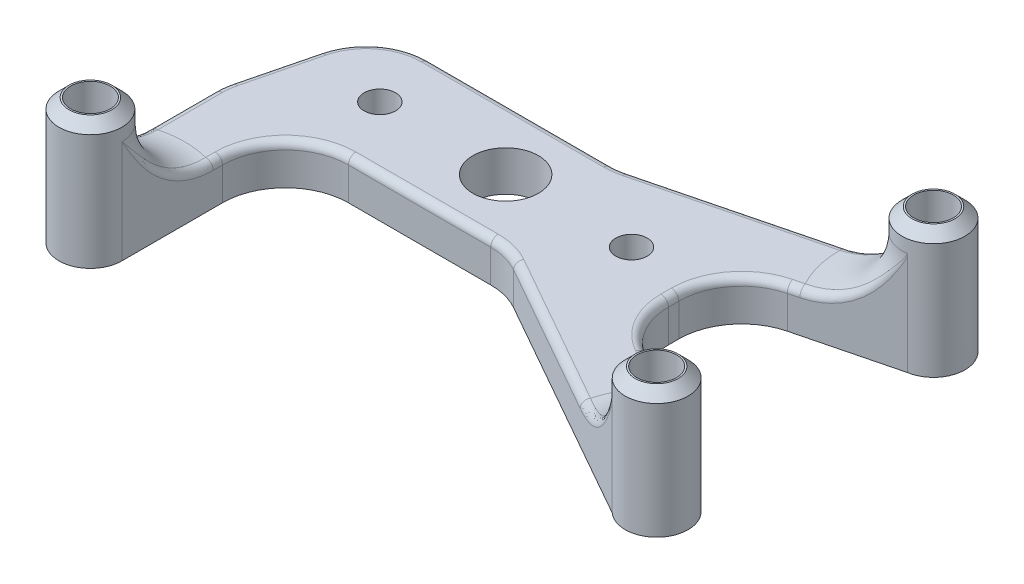
SolidWorks part; units mm, degrees
ref_plane "Front Plane" through (0, 0, 0) normal (0, 0, 1) x (1, 0, 0)
ref_plane "Top Plane" through (0, 0, 0) normal (0, 1, 0) x (1, 0, 0)
ref_plane "Right Plane" through (0, 0, 0) normal (1, 0, 0) x (0, 0, -1)
sketch "Sketch6" plane through (0, 0, 0) normal (0, 1, 0) x (1, 0, 0)
  line L1 (-19.05, -6.35) -> (19.05, -6.35)
  line L2 (-19.05, -6.35) -> (-19.05, 6.35)
  line L3 (-19.05, 6.35) -> (19.05, 6.35)
  line L4 (19.05, -6.35) -> (19.05, 6.35)
  line L5 (-19.05, -6.35) -> (19.05, 6.35) construction
  line L6 (-19.05, 6.35) -> (19.05, -6.35) construction
  point P0 (0, 0)
  dimension "D1" = 12.7
  dimension "D2" = 38.1
extrude "Boss-Extrude6" add sketch "Sketch6" along normal blind 3.175 separate body
sketch "Sketch4" plane through (0, 0, 0) normal (0, 1, 0) x (1, 0, 0)
  circle A0 centre (-19.05, -22.86) radius 3.175
  circle A1 centre (33.02, -17.78) radius 3.175
  circle A2 centre (33.02, 10.16) radius 3.175
  dimension "D1" = 6.35
  dimension "D2" = 6.35
  dimension "D3" = 6.35
  dimension "D4" = 52.07
  dimension "D5" = 5.08
  dimension "D6" = 27.94
  dimension "D7" = 10.16
  dimension "D8" = 33.02
extrude "Boss-Extrude5" add sketch "Sketch4" along normal blind 12.7
sketch "Sketch8" plane through (0, 0, 0) normal (0, 1, 0) x (1, 0, 0)
  line L2 (31.9779, 13.1591) -> (5.0632, 6.35)
  line L3 (19.05, 6.35) -> (-19.05, 6.35) construction
  line L4 (33.5193, 7.0245) -> (19.05, 3.3639)
  line L5 (19.05, -6.35) -> (19.05, 6.35) construction
  line L6 (19.05, 3.3639) -> (19.05, -6.35)
  line L7 (19.05, -6.35) -> (34.4379, -14.9392)
  line L8 (30.8958, -20.1397) -> (6.515, -6.35)
  line L9 (-19.05, -6.35) -> (19.05, -6.35) construction
  line L10 (6.515, -6.35) -> (-15.875, -6.35)
  line L11 (-15.875, -6.35) -> (-15.875, -22.86)
  line L12 (-22.225, -22.86) -> (-22.225, -6.35)
  line L13 (-22.225, -6.35) -> (-19.05, 6.35)
  line L14 (-19.05, 6.35) -> (5.0632, 6.35)
  circle A0 centre (33.02, 10.16) radius 3.175 construction
  arc A1 (33.5193, 7.0245) -> (31.9779, 13.1591) centre (33.02, 10.16) ccw
  circle A2 centre (33.02, -17.78) radius 3.175 construction
  arc A3 (34.4379, -14.9392) -> (30.8958, -20.1397) centre (33.02, -17.78) cw
  circle A4 centre (-19.05, -22.86) radius 3.175 construction
  arc A5 (-15.875, -22.86) -> (-22.225, -22.86) centre (-19.05, -22.86) cw
extrude "Boss-Extrude7" add sketch "Sketch8" along normal blind 4.064
fillet "Fillet1" radius 6.35 7 edges at (-15.875, 2.032, 6.35) (6.515, 2.032, 6.35) (19.05, 2.032, 6.35) (19.05, 2.032, -3.3639) (5.0632, 2.032, -6.35) (-22.225, 2.032, 6.35) (-19.05, 2.032, -6.35)
sketch "Sketch9" plane through (0, 4.064, 0) normal (0, 1, 0) x (1, 0, 0)
  circle A0 centre (-12.7, 0) radius 1.5875
  circle A1 centre (12.7, 0) radius 1.5875
  circle A2 centre (0, 0) radius 3.302
  dimension "D3" = 3.175
  dimension "D4" = 3.175
  dimension "D5" = 6.604
  dimension "D1" = 25.4
  dimension "D2" = 12.7
extrude "Cut-Extrude3" cut sketch "Sketch9" against normal through all
fillet "Fillet2" radius 6.35 3 edges at (-19.05, 4.064, 19.685) (30.3959, 4.064, 15.9927) (29.9407, 4.064, -9.3863)
sketch "Sketch10" plane through (0, 12.7, 0) normal (0, 1, 0) x (1, 0, 0)
  circle A0 centre (-19.05, -22.86) radius 2
  circle A1 centre (33.02, -17.78) radius 2
  circle A2 centre (33.02, 10.16) radius 2
  dimension "D1" = 4
  dimension "D2" = 4
  dimension "D3" = 4
extrude "Cut-Extrude4" cut sketch "Sketch10" against normal blind 5.7
chamfer "Chamfer1" distance 1.016 angle 45 3 edges at (33.02, 12.7, -6.985) (33.02, 12.7, 20.955) (-19.05, 12.7, 26.035)
fillet "Fillet3" radius 0.762 23 edges at (33.9762, 9.4892, 14.6815) (24.5142, 4.064, 9.4) (32.9555, 9.2707, -6.8819) (24.4639, 4.064, -4.7336) (20.3894, 4.064, -2.3212) (19.05, 4.064, 2.1009) (30.8401, 8.4731, -12.8713) (14.682, 4.064, -8.7834) (5.0571, 4.064, -6.3987) (-22.225, 5.5985, 18.5096) (-22.225, 4.064, 10.5057) (-22.1774, 4.064, 6.3559) (-21.1439, 4.064, 2.0258) (-17.9999, 4.064, -5.0051) (-15.875, 5.5985, 18.5096) (-15.875, 4.064, 13.2899) (-14.0151, 4.064, 8.2099) (29.7237, 7.8688, 19.4768) (15.8122, 4.064, 11.6085) (6.46, 4.064, 6.5592) (19.9239, 4.064, 5.837) (-4.9098, 4.064, -6.35) (-2.3407, 4.064, 6.35)
sketch "Sketch11" plane through (0, 7, 0) normal (0, 1, 0) x (1, 0, 0)
  circle A0 centre (-19.05, -22.86) radius 1.5875
  circle A1 centre (33.02, -17.78) radius 1.5875
  circle A2 centre (33.02, 10.16) radius 1.5875
  dimension "D1" = 3.175
  dimension "D2" = 3.175
  dimension "D3" = 3.175
extrude "Cut-Extrude5" cut sketch "Sketch11" against normal through all
